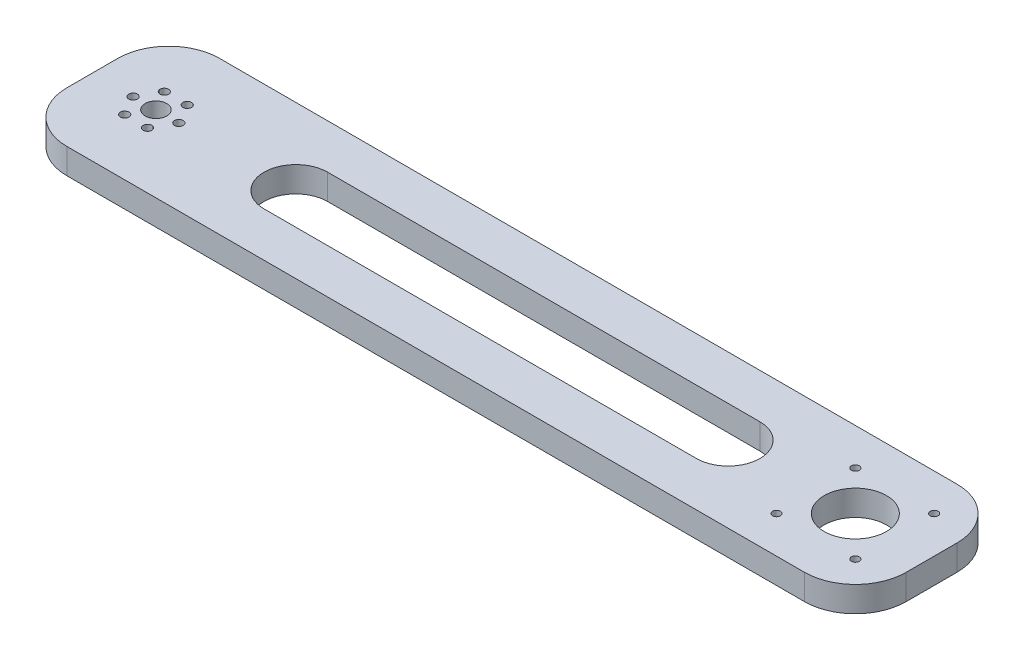
SolidWorks part; units mm, degrees
ref_plane "前视基准面" through (0, 0, 0) normal (0, 0, 1) x (1, 0, 0)
ref_plane "上视基准面" through (0, 0, 0) normal (0, 1, 0) x (1, 0, 0)
ref_plane "右视基准面" through (0, 0, 0) normal (1, 0, 0) x (0, 0, -1)
other "Configuration Table"
sketch "草图1" plane through (0, 0, 0) normal (0, 1, 0) x (1, 0, 0)
  line L1 (-165, -30) -> (165, -30)
  line L2 (-165, -30) -> (-165, 30)
  line L3 (-165, 30) -> (165, 30)
  line L4 (165, -30) -> (165, 30)
  line L5 (-165, -30) -> (165, 30) construction
  line L6 (-165, 30) -> (165, -30) construction
  point P0 (0, 0)
  dimension "D1" = 330
  dimension "D2" = 60
extrude "凸台-拉伸1" add sketch "草图1" along normal blind 10
fillet "圆角1" radius 20 4 edges at (165, 5, 30) (165, 5, -30) (-165, 5, -30) (-165, 5, 30)
sketch "草图5" plane through (0, 10, 0) normal (0, 1, 0) x (1, 0, 0)
  line L0 (165, 0) -> (-165, 0) construction
  line L1 (165, -10) -> (165, 10) construction
  line L2 (-165, 10) -> (-165, -10) construction
  circle A0 centre (135, 0) radius 12.25
  dimension "D1" = 24.5
  dimension "D2" = 30
extrude "切除-拉伸3" cut sketch "草图5" against normal blind 12
sketch "草图9" plane through (0, 0, 0) normal (0, -1, 0) x (1, 0, 0)
  circle A0 centre (119.5, 15.5) radius 1.55
  circle A1 centre (150.5, 15.5) radius 1.55
  circle A2 centre (150.5, -15.5) radius 1.55
  circle A3 centre (119.5, -15.5) radius 1.55
  dimension "D1" = 3.1
  dimension "D2" = 3.1
  dimension "D3" = 3.1
  dimension "D4" = 3.1
extrude "切除-拉伸6" cut sketch "草图9" against normal through all
sketch "草图11" plane through (0, 0, 0) normal (0, -1, 0) x (1, 0, 0)
  line L0 (-145, 30) -> (145, 30) construction
  line L1 (-165, -10) -> (-165, 10) construction
  circle A0 centre (-140, 0) radius 4.25
  dimension "D1" = 8.5
  dimension "D2" = 30
  dimension "D3" = 25
extrude "切除-拉伸8" cut sketch "草图11" against normal through all
sketch "草图15" plane through (0, 0, 0) normal (0, -1, 0) x (1, 0, 0)
  line L0 (-85, 0) -> (85, 0) construction
  line L1 (-85, 12.5) -> (85, 12.5)
  line L2 (-85, -12.5) -> (85, -12.5)
  arc A0 (-85, 12.5) -> (-85, -12.5) centre (-85, 0) ccw
  arc A1 (85, -12.5) -> (85, 12.5) centre (85, 0) ccw
  point P2 (0, 0)
  dimension "D1" = 170
  dimension "D2" = 25
extrude "切除-拉伸11" cut sketch "草图15" against normal through all
sketch "草图16" plane through (0, 0, 0) normal (0, -1, 0) x (1, 0, 0)
  circle A0 centre (-140, 0) radius 9 construction
  circle A1 centre (-149, 0) radius 1.7
  dimension "D1" = 18
  dimension "D2" = 3.4
extrude "切除-拉伸12" cut sketch "草图16" against normal through all
cosmetic thread "装饰螺纹线3" parameters "D2"=4.4
pattern_circular "阵列(圆周)1" count 6 every 60 about axis through (-140, 0, 0) along (0, -1, 0) of "切除-拉伸12"
cosmetic thread "装饰螺纹线4" parameters "D2"=4.4
